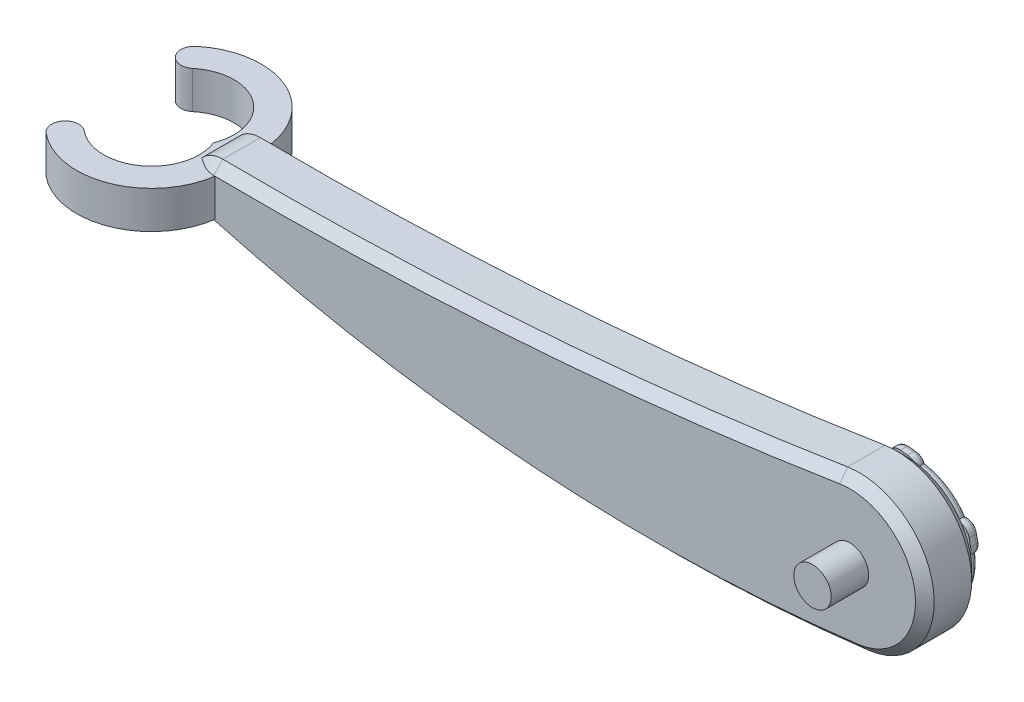
SolidWorks part; units mm, degrees
ref_plane "Front Plane" through (0, 0, 0) normal (0, 0, 1) x (1, 0, 0)
ref_plane "Top Plane" through (0, 0, 0) normal (0, 1, 0) x (1, 0, 0)
ref_plane "Right Plane" through (0, 0, 0) normal (1, 0, 0) x (0, 0, -1)
sketch "Sketch1" plane through (0, 0, 0) normal (0, 0, 1) x (1, 0, 0)
  line L0 (85, 0) -> (-85, 0) construction
  circle A0 centre (85, 0) radius 20
  circle A1 centre (-85, 0) radius 7.5
  arc A2 (-84.9221, 7.4996) -> (81.8718, 19.7538) centre (-74.5404, 1007.4457) ccw
  arc A3 (-86.9844, -7.2327) -> (87.4615, -19.8479) centre (32.0772, 426.7308) ccw
  point P4 (0, 0)
  dimension "D2" = 15
  dimension "D3" = 40
  dimension "D4" = 450
  dimension "D5" = 1000
  dimension "D1" = 170
extrude "Boss-Extrude2" add sketch "Sketch1" along normal mid plane 15 contours A1 | L0 A0 A2 A1 | A0 L0 A1 A3 | A0 region at (3.1113, -10.4688, 0) region at (6.4445, 6.0296, 0) region at (70.2222, 12.6217, 0) region at (-80.5807, -5.7951, 0)
chamfer "Chamfer1" distance 2.5 angle 45 8 edges at (-92.4276, 1.0397, 7.5) (-1.2686, 10.1337, 7.5) (104.8037, 2.7953, 7.5) (-0.3802, -22.0971, 7.5) (-0.3802, -22.0971, -7.5) (-92.4276, 1.0397, -7.5) (-1.2686, 10.1337, -7.5) (104.8037, 2.7953, -7.5)
sketch "Sketch3" plane through (0, 0, -7.5) normal (0, 0, -1) x (-1, 0, 0)
  circle A0 centre (-85, 0) radius 16.5
  dimension "D1" = 33
extrude "Boss-Extrude3" add sketch "Sketch3" along normal mid plane 5
sketch "Sketch4" plane through (0, 0, -10) normal (0, 0, -1) x (-1, 0, 0)
  line L0 (-85, 0) -> (-69.9921, -0.048)
  line L2 (-67.2448, 4.1787) -> (-68.028, 5.9265)
  line L3 (-72.2574, 7.3027) -> (-85, 0)
  line L4 (-85, 0) -> (-67.4523, 4.6417) construction
  line L5 (-85, 0) -> (-80.3166, 14.2585)
  line L6 (-88.0076, 14.3756) -> (-85, 0)
  line L7 (-83.4875, 18.1775) -> (-85.3918, 17.9727)
  line L8 (-85, 0) -> (-97.1134, 8.8603)
  line L9 (-99.6014, 1.5819) -> (-85, 0)
  line L10 (-101.8204, 7.0556) -> (-102.2142, 5.1812)
  line L11 (-85, 0) -> (-97.1698, -8.7825)
  line L12 (-91.0166, -13.3979) -> (-85, 0)
  line L13 (-96.9081, -13.8169) -> (-95.2471, -14.7705)
  line L14 (-85, 0) -> (-80.408, -14.2882)
  line L15 (-74.1171, -9.8623) -> (-85, 0)
  line L16 (-75.5392, -15.5949) -> (-74.1189, -14.3099)
  arc A0 (-68.028, 5.9265) -> (-72.2574, 7.3027) centre (-70.7657, 4.6998) ccw
  arc A1 (-67.2448, 4.1787) -> (-69.9921, -0.048) centre (-69.9825, 2.9519) cw
  arc A2 (-85.3918, 17.9727) -> (-88.0076, 14.3756) centre (-85.0711, 14.9899) ccw
  arc A3 (-83.4875, 18.1775) -> (-80.3166, 14.2585) centre (-83.1668, 15.1946) cw
  arc A4 (-102.2142, 5.1812) -> (-99.6014, 1.5819) centre (-99.2782, 4.5645) ccw
  arc A5 (-101.8204, 7.0556) -> (-97.1134, 8.8603) centre (-98.8845, 6.4389) cw
  arc A6 (-95.2471, -14.7705) -> (-91.0166, -13.3979) centre (-93.7533, -12.1689) ccw
  arc A7 (-96.9081, -13.8169) -> (-97.1698, -8.7825) centre (-95.4143, -11.2152) cw
  arc A8 (-74.1189, -14.3099) -> (-74.1171, -9.8623) centre (-76.1316, -12.0853) ccw
  arc A9 (-75.5392, -15.5949) -> (-80.408, -14.2882) centre (-77.5519, -13.3702) cw
  circle A10 centre (-85, 0) radius 2
  point P9 (-69.3828, 8.9501)
  point P36 (-85, 0)
  circle M13 centre (-85, 0) radius 16.5
  dimension "D3" = 3
  dimension "D4" = 3
  dimension "D6" = 4
  dimension "D1" = 30
  dimension "D2" = 18
  dimension "D5" = 5
extrude "Boss-Extrude5" add sketch "Sketch4" against normal up to surface (2.5 mm away) contours L4 A10 L0 A1 M13 | A10 L4 A0 L3 M13 | L4 A1 L2 M13 | L4 L2 A0 M13 | A10 L5 A3 A2 L6 M13 | A3 L7 A2 M13 | A10 L8 A5 A4 L9 M13 | A5 L10 A4 M13 | A10 L11 A7 A6 L12 M13 | A7 L13 A6 M13 | A10 L14 A9 A8 L15 M13 | A9 L16 A8 M13 region at (74.0061, 1.4226, -10) region at (74.7576, 4.1833, -10) region at (84.3813, 10.9644, -10) region at (95.2366, 3.9766, -10) region at (91.9453, -8.5068, -10) region at (79.0558, -9.2341, -10) region at (68.8747, 5.8512, -10) region at (67.9559, 2.7669, -10) region at (83.7877, 17.1, -10) region at (100.8884, 6.4371, -10) region at (96.0319, -13.1216, -10) region at (75.9296, -14.5467, -10) up to face at (101.5, 0, -7.5)
fillet "Fillet5" radius 1 20 edges at (93.7787, -15.1688, -10) (96.0776, -14.2937, -10) (98.2701, -12.1342, -10) (100.9775, -4.1193, -10) (102.1391, 3.6616, -10) (102.0173, 6.1184, -10) (100.6409, 8.8709, -10) (93.855, 13.9226, -10) (86.8139, 17.4318, -10) (84.4397, 18.0751, -10) (81.3966, 17.6167, -10) (74.4952, 12.7239, -10) (68.9819, 7.1118, -10) (67.6364, 5.0526, -10) (67.132, 2.0168, -10) (69.6527, -6.0588, -10) (73.2864, -13.0364, -10) (74.829, -14.9524, -10) (77.5604, -16.3702, -10) (86.0197, -16.4685, -10)
sketch "Sketch8" plane through (0, 0, 7.5) normal (0, 0, 1) x (1, 0, 0)
  circle A0 centre (85, 0) radius 5
  dimension "D1" = 10
extrude "Boss-Extrude6" add sketch "Sketch8" along normal blind 10
sketch "Sketch9" plane through (0, 0, 0) normal (0, 1, 0) x (1, 0, 0)
  line L0 (0, 0) -> (-84.9221, 0) construction
  line L1 (-84.9221, -5) -> (-84.9221, 5) construction
  line L2 (-92.5, 5) -> (-92.5, -5) construction
  line L3 (-84.9221, 0) -> (-92.5, 0)
  arc A0 (-84.9221, 0) -> (-117.1186, 20.0558) centre (-104.3764, 4.6404) ccw
  arc A1 (-92.5, 0) -> (-112.5, 14.4683) centre (-104.3764, 4.6404) ccw
  arc A2 (-117.1186, 20.0558) -> (-112.5, 14.4683) centre (-114.8093, 17.262) ccw
  arc A3 (-84.9221, 0) -> (-117.1186, -20.0558) centre (-104.3764, -4.6404) cw
  arc A4 (-117.1186, -20.0558) -> (-112.5, -14.4683) centre (-114.8093, -17.262) cw
  arc A5 (-92.5, 0) -> (-112.5, -14.4683) centre (-104.3764, -4.6404) cw
  point P10 (0, 0)
  dimension "D1" = 20
  dimension "D2" = 20
extrude "Boss-Extrude7" add sketch "Sketch9" along normal mid plane 10 contours L3 A5 A4 A3 | A0 A2 A1 L3 region at (-94.0241, 0, 21.2594) region at (-88.7111, 0, -0.4204)
